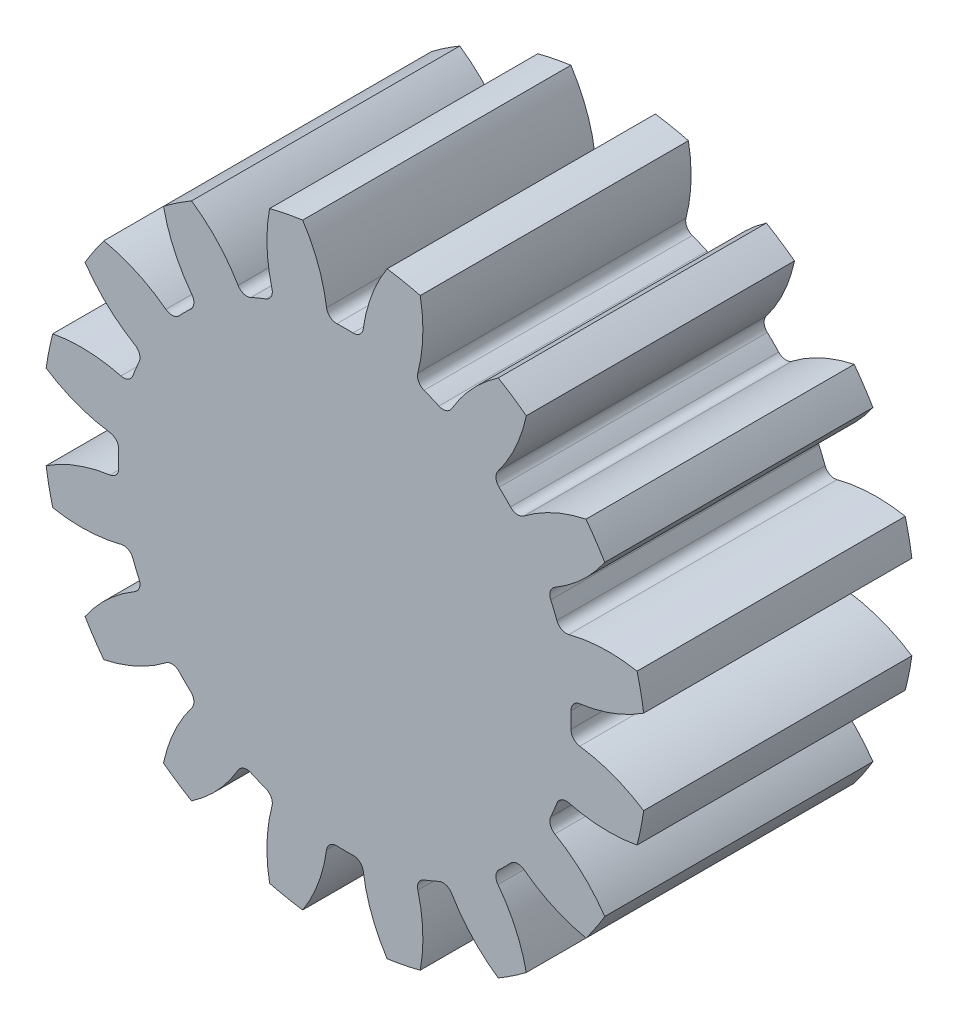
SolidWorks part; units mm, degrees
ref_plane "Front Plane" through (0, 0, 0) normal (0, 0, 1) x (1, 0, 0)
ref_plane "Top Plane" through (0, 0, 0) normal (0, 1, 0) x (1, 0, 0)
ref_plane "Right Plane" through (0, 0, 0) normal (1, 0, 0) x (0, 0, -1)
sketch "Sketch2" plane through (0, 0, 0) normal (0, 0, 1) x (1, 0, 0)
  circle A0 centre (0, 0) radius 10 construction
  circle A1 centre (0, 0) radius 11.25
  dimension "D1" = 20
  dimension "D2" = 22.5
extrude "Boss-Extrude1" add sketch "Sketch2" along normal mid plane 10 contours A1
sketch "Sketch3" plane through (0, 0, 0) normal (0, 0, 1) x (1, 0, 0)
  line L0 (0, 11.25) -> (0, 0) construction
  line L1 (0, 0) -> (4.3052, 10.3936) construction
  line L2 (0, 0) -> (2.1948, 11.0338) construction
  line L3 (-0.6474, 8.4126) -> (0, 0) construction
  line L4 (-0.9802, 9.9518) -> (0.9802, 9.9518) construction
  line L5 (0.9802, 9.9518) -> (2.9028, 9.5694) construction
  line L6 (-1.4199, 11.16) -> (0, 7.2588) construction
  circle A0 centre (0, 0) radius 8.75 construction
  arc A1 (0.6474, 8.4126) -> (-0.6474, 8.4126) centre (0, 0) ccw
  circle A2 centre (0, 0) radius 11.25 construction
  circle A3 centre (0, 0) radius 10 construction
  arc A4 (-1.574, 11.1393) -> (-0.6474, 8.4126) centre (-6.4322, 7.9675) cw
  arc A5 (1.574, 11.1393) -> (0.6474, 8.4126) centre (6.4322, 7.9675) ccw
  arc A6 (1.574, 11.1393) -> (-1.574, 11.1393) centre (0, 0) ccw
  dimension "D4" = 20
  dimension "D1" = 22.5
  dimension "D2" = 2.5
  dimension "D3" = 2.8125
  dimension "D5" = 20
extrude "Cut-Extrude1" cut sketch "Sketch3" against normal through all both and the other way through all
fillet "Fillet1" radius 0.375 2 edges at (0.6474, 8.4126, 0) (-0.6474, 8.4126, 0)
ref_axis "Axis1" through (0, 0, -11) along (0, 0, 1)
pattern_circular "CirPattern1" count 16 over 360 about axis through (0, 0, -11) along (0, 0, 1) of "Cut-Extrude1", "Fillet1"
sketch "Sketch4" plane through (0, 0, -5) normal (0, 0, -1) x (-1, 0, 0)
  line L0 (-1.5468, 1.9) -> (1.5468, 1.9)
  arc A0 (-1.5468, 1.9) -> (1.5468, 1.9) centre (0, 0) ccw
  dimension "D1" = 4.9
  dimension "D2" = 1.9
extrude "Cut-Extrude2" cut sketch "Sketch4" against normal blind 9
equation "\"Module\" = 1.25mm"
equation "\"Number of teeth\"= 16"
equation "\"pressure angle\"= 20"
equation "\"D1@Sketch2\"=\"Module\"*\"Number of teeth\""
equation "\"D2@Sketch2\"=(\"Number of teeth\"+2) *\"Module\""
equation "\"D1@Sketch3\"=360 /\"Number of teeth\""
equation "\"D2@Sketch3\"=\"Module\"*2"
equation "\"D3@Sketch3\"=\"Module\" *if( \"Module\"=> 1.25,2.25,2.4)"
equation "\"D5@Sketch3\"=\"pressure angle\""
equation "\"D4@Sketch3\"=\"Module\"*\"Number of teeth\""
equation "\"D1@CirPattern1\"=\"Number of teeth\""
equation "\"D1@Fillet1\"=0.3 *\"Module\""
